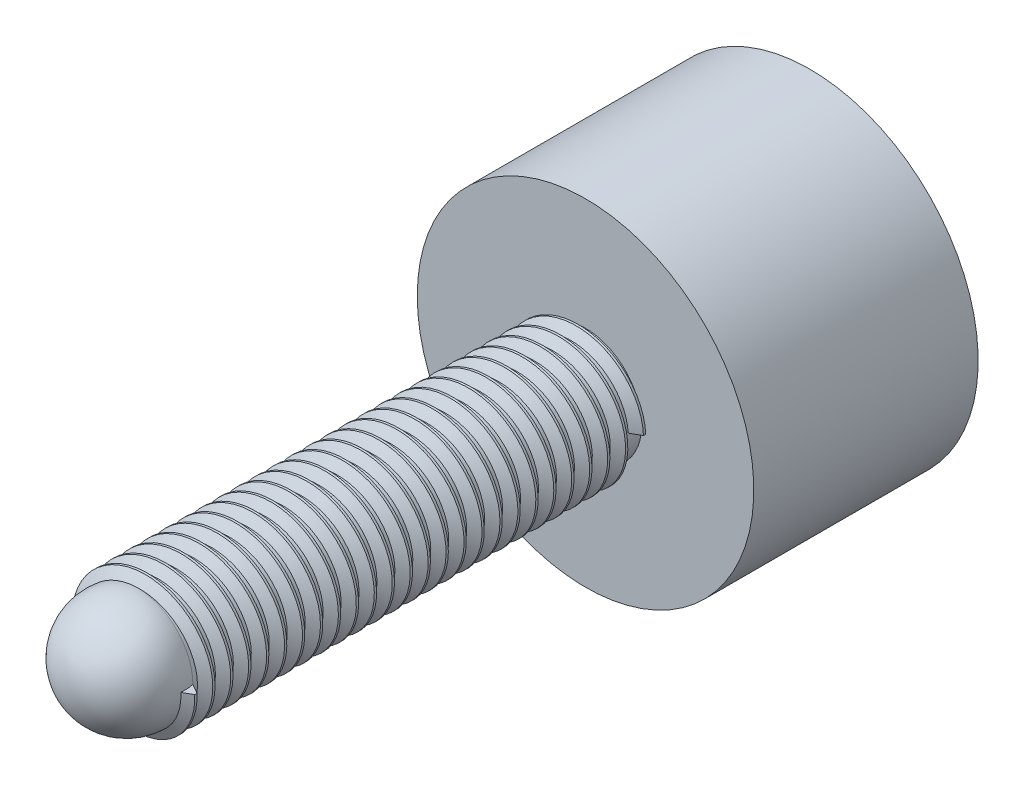
SolidWorks part; units mm, degrees
ref_plane "Front Plane" through (0, 0, 0) normal (0, 0, 1) x (1, 0, 0)
ref_plane "Top Plane" through (0, 0, 0) normal (0, 1, 0) x (1, 0, 0)
ref_plane "Right Plane" through (0, 0, 0) normal (1, 0, 0) x (0, 0, -1)
sketch "Sketch1" plane through (0, 0, 0) normal (0, 0, 1) x (1, 0, 0)
  circle A0 centre (0, 0) radius 2.5
  dimension "D1" = 5
extrude "Boss-Extrude1" add sketch "Sketch1" along normal blind 20
dome "Dome1" faces to dome 1 distance 3 reverse direction no elliptical dome no face at (2.5, 0, 20) parameters "D1"=3
thread "Thread1" pitch 0.8 method extrude profile "Thread Profile1" start angle 0, offset 0, length 0, pitch 0.8, diameter 5
ref_plane "Plane1" through (2.5, 0, 0) normal (0, -1, 0) x (1, 0, 0)
sketch "Thread Profile1" plane through (2.5, 0, 0) normal (0, -1, 0) x (1, 0, 0)
  line L0 (0, 0) -> (0, 0.8) construction
  line L1 (0, 0) -> (0.433, 0.25)
  line L2 (0.433, 0.25) -> (0.433, 0.35)
  line L3 (0.433, 0.35) -> (0, 0.6)
  line L4 (0.433, 0.3) -> (0, 0.3) construction
  line L11 (0, 0) -> (0, 0.6)
  point P2 (0, 0)
  dimension "Pitch" = 0.8
  dimension "Profile_Angle" = 60
  dimension "Profile_Land" = 0.1
  dimension "Profile_Height" = 0.433
sketch "Sketch5" plane through (0, 0, 0) normal (0, 0, -1) x (-1, 0, 0)
  circle A2 centre (0, 0) radius 7.5
  circle A3 centre (0, 0) radius 7.5
  dimension "D1" = 5
extrude "Boss-Extrude2" add sketch "Sketch5" along normal blind 10
sketch "Sketch6" plane through (0, 0, -10) normal (0, 0, -1) x (-1, 0, 0)
  line L1 (-2, -3) -> (2, -3)
  line L2 (-2, -3) -> (-2, 3)
  line L3 (-2, 3) -> (2, 3)
  line L4 (2, -3) -> (2, 3)
  line L5 (-2, -3) -> (2, 3) construction
  line L6 (-2, 3) -> (2, -3) construction
  point P0 (0, 0)
  dimension "D1" = 6
  dimension "D2" = 4
extrude "Cut-Extrude1" cut sketch "Sketch6" against normal blind 8
